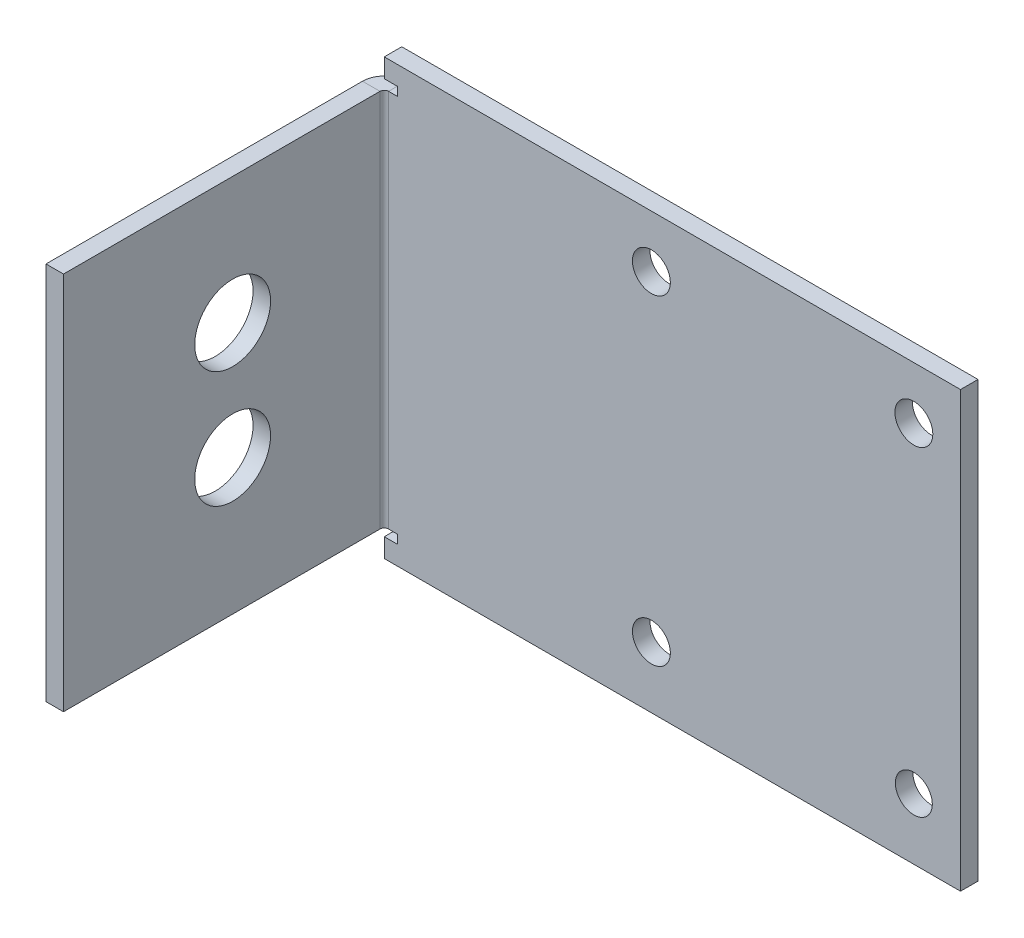
SolidWorks part; units mm, degrees
note: The reader was unsure of these and kept them because the rebuilt part matched: flange length of "Kenar-Flanş1".
ref_plane "Ön Düzlem" through (0, 0, 0) normal (0, 0, 1) x (1, 0, 0)
ref_plane "Üst Düzlem" through (0, 0, 0) normal (0, 1, 0) x (1, 0, 0)
ref_plane "Sağ Düzlem" through (0, 0, 0) normal (1, 0, 0) x (0, 0, -1)
sketch "Çizim1" plane through (0, 0, 0) normal (0, 0, 1) x (1, 0, 0)
  line L1 (-49.4, -37.25) -> (49.4, -37.25)
  line L2 (-49.4, -37.25) -> (-49.4, 37.25)
  line L3 (-49.4, 37.25) -> (49.4, 37.25)
  line L4 (49.4, -37.25) -> (49.4, 37.25)
  line L5 (-49.4, -37.25) -> (49.4, 37.25) construction
  line L6 (-49.4, 37.25) -> (49.4, -37.25) construction
  point P0 (0, 0)
  dimension "D1" = 98.8
  dimension "D2" = 74.5
base flange "Taban-Flanş1" sketch "Çizim1" thickness 3 reverse thickness direction no parameters "D1"=0.7366
edge flange "Kenar-Flanş1" sketch "Çizim8" flange angle 90 flange length 58 flange position material outside bend radius 0.7366 thickness 3 relief rectangular parameters "D6"=10
sketch "Çizim8" plane through (-49.4, 0, 0) normal (-1, 0, 0) x (0, -1, 0)
  line L0 (-37.25, 0) -> (37.25, 0) construction
  line L1 (-32.5, 0) -> (32.5, 0)
  line L2 (-32.5, 0) -> (-32.5, 55)
  line L3 (-32.5, 55) -> (32.5, 55)
  line L4 (32.5, 55) -> (32.5, 0)
  point P8 (0, 0)
  point P9 (0, 0)
  dimension "D1" = 55
  dimension "D2" = 65
bend "KenarBükümü1" bend radius 0.7366 bend angle 90 parameters "D5"=1
sketch "Çizim9" plane through (-49.4, 0, 0) normal (1, 0, 0) x (0, 0, -1)
  circle A0 centre (-26, 10.75) radius 6.5
  circle A1 centre (-26, -9.25) radius 6.5
  dimension "D1" = 13
  dimension "D2" = 13
extrude "Kes-Ekstrüzyon1" cut sketch "Çizim9" against normal blind 10 normal cut yes
ref_plane "Düzlem1" through (41.4, 31.5, -3) normal (-1, 0, 0) x (0, 0, 1)
sketch "Çizim11" plane through (0, 0, 0) normal (0, 0, 1) x (1, 0, 0)
  circle A0 centre (41.4, 28.25) radius 3.25
  circle A1 centre (-3.6, 28.25) radius 3.25
  circle A2 centre (-3.6, -26.75) radius 3.25
  circle A3 centre (41.4, -26.75) radius 3.1664
extrude "Kes-Ekstrüzyon2" cut sketch "Çizim11" against normal blind 10 normal cut yes
sketch "Büküm-Çizgileri1" [suppressed] plane through (0, 0, 0) normal (0, 1, 0) x (1, 0, 0)
sketch "Sınırlandırma-Kutusu1" [suppressed] plane through (0, 0, 0) normal (0, 1, 0) x (1, 0, 0)
sheet metal parameters "Sac-Levha1" thickness 3 parameters "D1"=0.7366
flat pattern "Düz-Çoğaltma1" [suppressed]
sketch "Büküm-Çizgileri2" plane through (0, 0, 0) normal (0, 1, 0) x (1, 0, 0)
sketch3d "Sınırlandırma-Kutusu2" [suppressed]
  line L0 (49.4, -37.25, 0) -> (-49.4, -37.25, 0) construction
  line L1 (49.4, 37.25, 0) -> (-49.4, 37.25, 0) construction
  line L2 (49.4, -37.25, 0) -> (49.4, 37.25, 0) construction
  line L3 (-49.4, -37.25, 0) -> (-49.4, 37.25, 0) construction
sheet metal parameters "Sac-Levha2" thickness 3 parameters "D1"=0.7366
flat pattern "Düz-Çoğaltma1"
sketch "Büküm-Çizgileri2" plane through (0, 0, 0) normal (0, 0, 1) x (1, 0, 0)
  line L0 (-50.42, 32.5) -> (-50.42, -32.5) construction
  line L1 (-50.42, 32.5) -> (-50.42, -32.5) construction
sketch3d "Sınırlandırma-Kutusu2" [suppressed]
  line L0 (-106.44, -37.25, 0) -> (49.4, -37.25, 0) construction
  line L1 (-106.44, 37.25, 0) -> (49.4, 37.25, 0) construction
  line L2 (-106.44, -37.25, 0) -> (-106.44, 37.25, 0) construction
  line L3 (49.4, -37.25, 0) -> (49.4, 37.25, 0) construction
bend of the flat pattern "Düzleştirme TipiKenarBükümü1>1"
sheet metal parameters "Sac-Levha3" thickness 3 parameters "D1"=0.7366
flat pattern "Düz-Çoğaltma1"
sketch "Büküm-Çizgileri2" plane through (0, 0, 0) normal (0, 0, 1) x (1, 0, 0)
  line L0 (-50.42, 32.5) -> (-50.42, -32.5) construction
  line L1 (-50.42, 32.5) -> (-50.42, -32.5) construction
sketch3d "Sınırlandırma-Kutusu2" [suppressed]
  line L0 (-106.44, -37.25, 0) -> (49.4, -37.25, 0) construction
  line L1 (-106.44, 37.25, 0) -> (49.4, 37.25, 0) construction
  line L2 (-106.44, -37.25, 0) -> (-106.44, 37.25, 0) construction
  line L3 (49.4, -37.25, 0) -> (49.4, 37.25, 0) construction
bend of the flat pattern "Düzleştirme TipiKenarBükümü1>1"
sheet metal parameters "Sac-Levha4" thickness 3 parameters "D1"=0.7366
flat pattern "Düz-Çoğaltma1"
sketch "Büküm-Çizgileri2" plane through (0, 0, 0) normal (0, 0, 1) x (1, 0, 0)
  line L0 (-50.42, 32.5) -> (-50.42, -32.5) construction
  line L1 (-50.42, 32.5) -> (-50.42, -32.5) construction
sketch3d "Sınırlandırma-Kutusu2" [suppressed]
  line L0 (-106.44, -37.25, 0) -> (49.4, -37.25, 0) construction
  line L1 (-106.44, 37.25, 0) -> (49.4, 37.25, 0) construction
  line L2 (-106.44, -37.25, 0) -> (-106.44, 37.25, 0) construction
  line L3 (49.4, -37.25, 0) -> (49.4, 37.25, 0) construction
bend of the flat pattern "Düzleştirme TipiKenarBükümü1>1"
